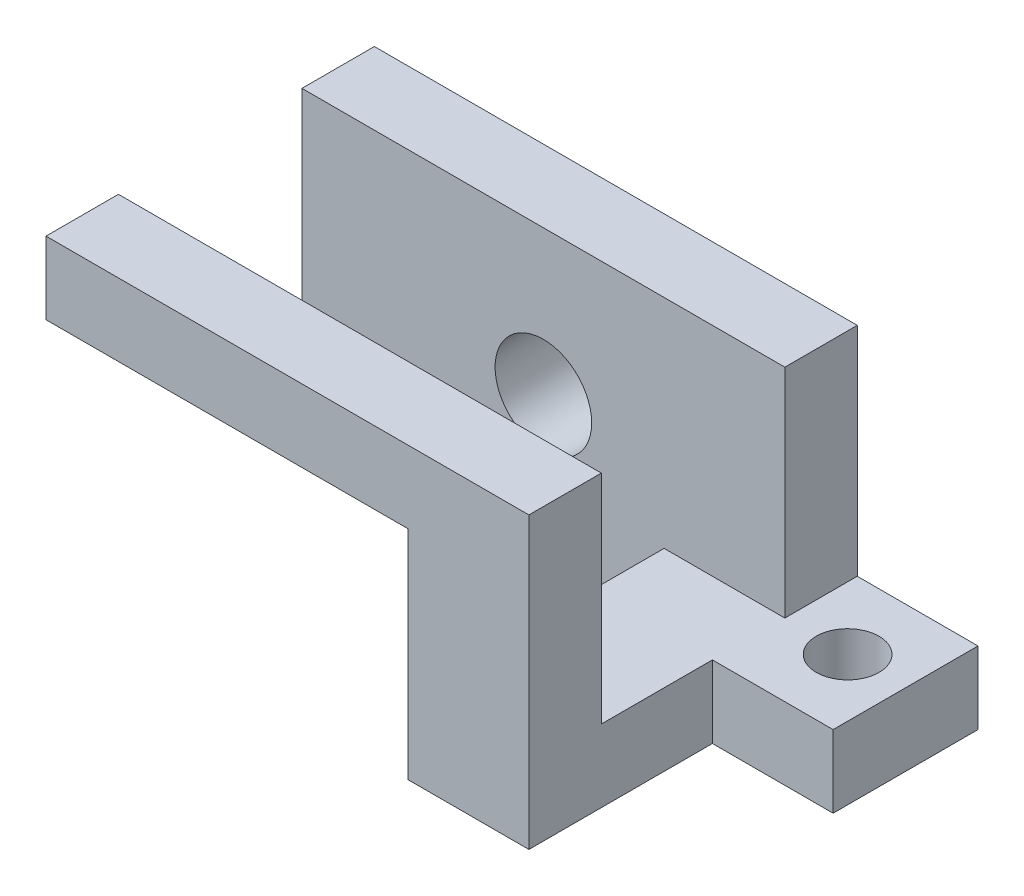
SolidWorks part; units mm, degrees
ref_plane "Front Plane" through (0, 0, 0) normal (0, 0, 1) x (1, 0, 0)
ref_plane "Top Plane" through (0, 0, 0) normal (0, 1, 0) x (1, 0, 0)
ref_plane "Right Plane" through (0, 0, 0) normal (1, 0, 0) x (0, 0, -1)
sketch "Sketch1" plane through (0, 0, 0) normal (0, 0, 1) x (1, 0, 0)
  line L0 (0, 0) -> (0, -30)
  line L1 (-50, -30) -> (50, -30)
  line L2 (-50, 30) -> (50, 30)
  line L3 (50, -30) -> (75, -30)
  line L4 (75, -30) -> (75, -15)
  line L5 (75, -15) -> (50, -15)
  line L6 (50, -15) -> (50, 30)
  line L7 (-50, -30) -> (-50, 30)
  line L8 (75, -15) -> (25, -15)
  line L9 (25, -15) -> (25, -30)
  line L10 (50, -15) -> (50, -30)
  circle A0 centre (0, 0) radius 10
  dimension "D1" = 20
  dimension "D2" = 100
  dimension "D3" = 60
  dimension "D4" = 15
extrude "Boss-Extrude1" add sketch "Sketch1" along normal blind 15 contours A0 L1 L9 L8 L6 L2 L7 region at (-25, -28.8338, 0)
extrude "Boss-Extrude2" add sketch "Sketch1<5>" along normal blind 30 contours L10 L8 L9 L1 | L5 L10 L3 L4 region at (37.5, -22.5, 0) region at (62.5, -22.5, 0)
sketch "Sketch1<5>" plane through (0, 0, 0) normal (0, 0, 1) x (1, 0, 0) same geometry as "Sketch1"
extrude "Boss-Extrude3" add sketch "Sketch1<6>" along normal blind 53 contours L10 L8 L9 L1 region at (37.5, -22.5, 0)
sketch "Sketch1<6>" plane through (0, 0, 0) normal (0, 0, 1) x (1, 0, 0) same geometry as "Sketch1"
sketch "Sketch2" plane through (0, 0, 53) normal (0, 0, 1) x (1, 0, 0)
  line L0 (50, -30) -> (50, 30)
  line L1 (50, 30) -> (-50, 30)
  line L2 (-50, 30) -> (-50, 15)
  line L3 (-50, -30) -> (-50, 30) construction
  line L4 (-50, 15) -> (25, 15)
  line L5 (25, 15) -> (25, -30)
  line L6 (25, -30) -> (50, -30)
extrude "Boss-Extrude4" add sketch "Sketch2" along normal blind 15
sketch "Sketch3" plane through (0, -15, 0) normal (0, 1, 0) x (1, 0, 0)
  line L0 (75, 0) -> (63, 0)
  line L1 (75, 0) -> (50, 0) construction
  line L2 (63, 0) -> (63, -15)
  circle A0 centre (63, -15) radius 6.5
extrude "Cut-Extrude1" cut sketch "Sketch3" against normal blind 15 contours A0 region at (58.5338, -15, 19.4662)
